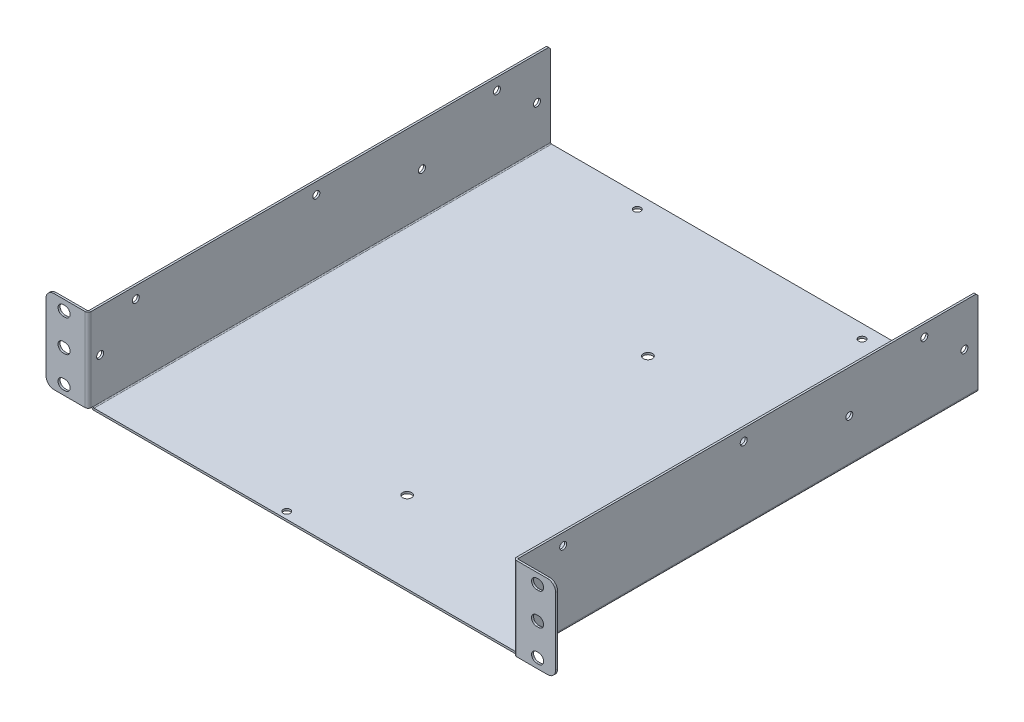
SolidWorks part; units mm, degrees
note: The reader was unsure of these and kept them because the rebuilt part matched: flange length of "Edge-Flange3", "Edge-Flange4", "Edge-Flange5", "Edge-Flange6".
ref_plane "Front Plane" through (0, 0, 0) normal (0, 0, 1) x (1, 0, 0)
ref_plane "Top Plane" through (0, 0, 0) normal (0, 1, 0) x (1, 0, 0)
ref_plane "Right Plane" through (0, 0, 0) normal (1, 0, 0) x (0, 0, -1)
sketch "Sketch1" plane through (0, 0, 0) normal (0, 1, 0) x (1, 0, 0)
  line L5 (-107, 115.25) -> (107, 115.25)
  line L6 (-107, 115.25) -> (-107, -115.25)
  line L7 (-107, -115.25) -> (107, -115.25)
  line L8 (107, 115.25) -> (107, -115.25)
  line L9 (-107, 115.25) -> (107, -115.25) construction
  line L10 (-107, -115.25) -> (107, 115.25) construction
  point P0 (0, 0)
  dimension "D1" = 214
  dimension "D2" = 230.5
base flange "Base-Flange1" sketch "Sketch1" thickness 1 reverse thickness direction no parameters "D1"=8
edge flange "Edge-Flange3" sketch "Sketch14" flange angle 90 flange length 43 flange position material inside bend radius 0.5 thickness 1 relief rectangular parameters "D6"=10
sketch "Sketch14" plane through (-107, 0, 0) normal (-1, 0, 0) x (0, 0, 1)
  line L0 (-115.25, 0) -> (115.25, 0) construction
  line L1 (-115.25, 0) -> (115.25, 0)
  line L2 (-115.25, 0) -> (-115.25, 42)
  line L3 (-115.25, 42) -> (115.25, 42)
  line L4 (115.25, 42) -> (115.25, 0)
bend "EdgeBend3" bend radius 0.5 bend angle 90 parameters "D5"=1
edge flange "Edge-Flange4" sketch "Sketch17" flange angle 90 flange length 43 flange position material inside bend radius 0.5 thickness 1 relief rectangular parameters "D6"=10
sketch "Sketch17" plane through (107, 0, 0) normal (1, 0, 0) x (0, 0, -1)
  line L0 (-115.25, 0) -> (115.25, 0) construction
  line L1 (-115.25, 0) -> (115.25, 0)
  line L2 (-115.25, 0) -> (-115.25, 42)
  line L3 (-115.25, 42) -> (115.25, 42)
  line L4 (115.25, 42) -> (115.25, 0)
bend "EdgeBend4" bend radius 0.5 bend angle 90 parameters "D5"=2
edge flange "Edge-Flange5" sketch "Sketch20" flange angle 90 flange length 21 flange position material inside bend radius 0.5 thickness 1 relief none parameters "D6"=10
sketch "Sketch20" plane through (107, 0, 115.25) normal (0, 0, 1) x (0, -1, 0)
  line L2 (-42, 0) -> (-42, 20)
  line L3 (-42, 20) -> (-0.5, 20)
  line L4 (-0.5, 20) -> (-0.5, 0)
  line L7 (-42, 0) -> (-0.5, 0) construction
  line L8 (-42, 0) -> (-0.5, 0)
bend "EdgeBend5" bend radius 0.5 bend angle 90 parameters "D5"=3
edge flange "Edge-Flange6" sketch "Sketch23" flange angle 90 flange length 21 flange position material inside bend radius 0.5 thickness 1 relief none parameters "D6"=10
sketch "Sketch23" plane through (-107, 0, 115.25) normal (0, 0, 1) x (0, 1, 0)
  line L0 (0.5, 0) -> (42, 0) construction
  line L1 (0.5, 0) -> (42, 0)
  line L2 (0.5, 0) -> (0.5, 20)
  line L3 (0.5, 20) -> (42, 20)
  line L4 (42, 20) -> (42, 0)
bend "EdgeBend6" bend radius 0.5 bend angle 90 parameters "D5"=4
fillet "Fillet1" radius 4 4 edges at (-127, 0.5, 114.75) (-127, 42, 114.75) (127, 0.5, 114.75) (127, 42, 114.75)
sketch "Sketch24" plane through (0, -1, 0) normal (0, -1, 0) x (1, 0, 0)
  line L0 (107, -115.25) -> (107, 113.75) construction
  line L1 (-107, 115.25) -> (107, 115.25)
  line L2 (-107, 115.25) -> (-107, 112.75)
  line L3 (-107, 112.75) -> (107, 112.75)
  line L4 (107, 115.25) -> (107, 112.75)
  dimension "D1" = 2.5
extrude "Cut-Extrude1" cut sketch "Sketch24" against normal up to surface (1.5 mm away) normal cut yes up to face at (115.25, 0.5, 114.75)
sketch "Sketch26" plane through (0, 0, 115.25) normal (0, 0, 1) x (1, 0, 0)
  line L0 (-118, 37) -> (-118, 5.24) construction
  line L1 (-118, 21.12) -> (-120.5, 21.12) construction
  line L3 (0, 0) -> (0, 21.12) construction
  line L4 (105.5, 0) -> (-105.5, 0) construction
  line L5 (0, 21.12) -> (-118, 21.12) construction
  line L6 (-118, 37) -> (-118, 42) construction
  line L7 (-107.5, 42) -> (-123, 42) construction
  circle A0 centre (-118, 37) radius 2.5
  circle A1 centre (-118, 5.24) radius 2.5
  circle A2 centre (-118, 21.12) radius 2.5
  circle A3 centre (118, 5.24) radius 2.5
  circle A4 centre (118, 21.12) radius 2.5
  circle A5 centre (118, 37) radius 2.5
  dimension "D1" = 31.76
  dimension "D2" = 5
  dimension "D3" = 118
  dimension "D4" = 5
extrude "Cut-Extrude2" cut sketch "Sketch26" against normal blind 10 normal cut yes
sketch "Sketch27" plane through (107, 0, 0) normal (1, 0, 0) x (0, 0, -1)
  circle A0 centre (-91.5, 36.25) radius 1.75
  circle A1 centre (-1.5, 36.25) radius 1.75
  circle A2 centre (88.5, 36.25) radius 1.75
  dimension "D1" = 3.5
extrude "Cut-Extrude3" cut sketch "Sketch27" against normal through all normal cut yes
sketch "Sketch28" plane through (0, -1, 0) normal (0, -1, 0) x (1, 0, 0)
  circle A0 centre (10, 72.25) radius 2.25
  circle A1 centre (85, 72.25) radius 2.25
  circle A2 centre (10, -47.75) radius 2.25
  circle A3 centre (85, -47.75) radius 2.25
  dimension "D1" = 4.5
extrude "Cut-Extrude4" cut sketch "Sketch28" against normal through all normal cut yes
sketch "Sketch29" plane through (0, 0, 0) normal (0, 1, 0) x (1, 0, 0)
  circle A0 centre (56, 108.45) radius 1.75
  circle A1 centre (-56, 108.45) radius 1.75
  dimension "D1" = 3.5
extrude "Cut-Extrude5" cut sketch "Sketch29" against normal through all normal cut yes
sketch "Sketch30" plane through (-107, 0, 0) normal (-1, 0, 0) x (0, 0, 1)
  line L0 (-115.25, 42) -> (-115.25, 0.5) construction
  line L1 (112.75, -1) -> (-115.25, -1) construction
  circle A0 centre (-51.1, 21) radius 1.75
  dimension "D1" = 64.15
  dimension "D3" = 3.5
  dimension "D2" = 22
extrude "Cut-Extrude6" cut sketch "Sketch30" against normal through all normal cut yes
sketch "Sketch31" plane through (-107, 0, 0) normal (-1, 0, 0) x (0, 0, 1)
  circle A0 centre (-108.45, 21) radius 1.75
  dimension "D1" = 3.5
extrude "Cut-Extrude7" cut sketch "Sketch31" against normal through all normal cut yes
chamfer "Chamfer1" distance 1 angle 45 2 edges at (106.5, 42, -115.25) (-106.5, 42, -115.25)
sketch "Sketch32" plane through (0, 0, 114.25) normal (0, 0, -1) x (-1, 0, 0)
  line L0 (117.5, 37) -> (118.5, 37) construction
  line L1 (117.5, 39.5) -> (118.5, 39.5)
  line L2 (117.5, 34.5) -> (118.5, 34.5)
  line L3 (117.5, 21.12) -> (118.5, 21.12) construction
  line L4 (117.5, 23.62) -> (118.5, 23.62)
  line L5 (117.5, 18.62) -> (118.5, 18.62)
  line L6 (117.5, 5.24) -> (118.5, 5.24) construction
  line L7 (117.5, 7.74) -> (118.5, 7.74)
  line L8 (117.5, 2.74) -> (118.5, 2.74)
  line L9 (0, -1) -> (0, -11.9276) construction
  line L10 (-105.5, -1) -> (105.5, -1) construction
  arc A0 (117.5, 39.5) -> (117.5, 34.5) centre (117.5, 37) ccw
  arc A1 (118.5, 34.5) -> (118.5, 39.5) centre (118.5, 37) ccw
  arc A3 (117.5, 23.62) -> (117.5, 18.62) centre (117.5, 21.12) ccw
  arc A4 (118.5, 18.62) -> (118.5, 23.62) centre (118.5, 21.12) ccw
  arc A5 (117.5, 7.74) -> (117.5, 2.74) centre (117.5, 5.24) ccw
  arc A6 (118.5, 2.74) -> (118.5, 7.74) centre (118.5, 5.24) ccw
  point P2 (118, 37)
  point P15 (118, 21.12)
  point P22 (118, 5.24)
  dimension "D2" = 2.5
  dimension "D3" = 3
  dimension "D1" = 1
  dimension "D4" = 15.88
extrude "Cut-Extrude8" cut sketch "Sketch32" against normal through all normal cut yes
mirror "Mirror1" about plane through (0, 0, 0) normal (1, 0, 0) of "Cut-Extrude8"
sketch "Sketch33" plane through (0, -1, 0) normal (0, -1, 0) x (1, 0, 0)
  circle A0 centre (-13, 109.25) radius 1.75
  dimension "D1" = 3.5
extrude "Cut-Extrude9" cut sketch "Sketch33" against normal through all normal cut yes
sketch "Sketch34" plane through (-107, 0, 0) normal (-1, 0, 0) x (0, 0, 1)
  circle A0 centre (109.25, 21) radius 1.75
  dimension "D1" = 3.5
extrude "Cut-Extrude10" cut sketch "Sketch34" against normal through all normal cut yes
sketch "Bend-Lines1" [suppressed] plane through (0, 0, 0) normal (0, 1, 0) x (1, 0, 0)
sketch "Bounding-Box1" [suppressed] plane through (0, 0, 0) normal (0, 1, 0) x (1, 0, 0)
sheet metal parameters "Sheet-Metal1" thickness 1 parameters "D1"=8
flat pattern "Flat-Pattern1" [suppressed]
sketch "Bend-Lines2" plane through (0, 0, 0) normal (0, 1, 0) x (1, 0, 0)
sketch3d "Bounding-Box2" [suppressed]
  line L0 (-107, 115.25, 0) -> (-107, -115.25, 0) construction
  line L1 (107, 115.25, 0) -> (107, -115.25, 0) construction
  line L2 (-107, 115.25, 0) -> (107, 115.25, 0) construction
  line L3 (-107, -115.25, 0) -> (107, -115.25, 0) construction
sheet metal parameters "Sheet-Metal4" thickness 1 parameters "D1"=8
flat pattern "Flat-Pattern1"
sketch "Bend-Lines2" plane through (0, 0, 0) normal (0, 1, 0) x (1, 0, 0)
  line L0 (-107.2854, 115.25) -> (-107.2854, -115.25) construction
  line L1 (-107.2854, 115.25) -> (-107.2854, -115.25) construction
sketch3d "Bounding-Box2" [suppressed]
  line L0 (107, -115.25, 0) -> (-150.5708, -115.25, 0) construction
  line L1 (107, 115.25, 0) -> (-150.5708, 115.25, 0) construction
  line L2 (107, -115.25, 0) -> (107, 115.25, 0) construction
  line L3 (-150.5708, -115.25, 0) -> (-150.5708, 115.25, 0) construction
bend of the flat pattern "Flatten-<EdgeBend3>1"
sheet metal parameters "Sheet-Metal5" thickness 1 parameters "D1"=8
flat pattern "Flat-Pattern1"
sketch "Bend-Lines2" plane through (0, 0, 0) normal (0, 1, 0) x (1, 0, 0)
  line L0 (-107.2854, 115.25) -> (-107.2854, -115.25) construction
  line L1 (-107.2854, 115.25) -> (-107.2854, -115.25) construction
  line L2 (107.2854, -115.25) -> (107.2854, 115.25) construction
  line L3 (107.2854, -115.25) -> (107.2854, 115.25) construction
sketch3d "Bounding-Box2" [suppressed]
  line L0 (150.5708, -115.25, 0) -> (-150.5708, -115.25, 0) construction
  line L1 (150.5708, 115.25, 0) -> (-150.5708, 115.25, 0) construction
  line L2 (150.5708, -115.25, 0) -> (150.5708, 115.25, 0) construction
  line L3 (-150.5708, -115.25, 0) -> (-150.5708, 115.25, 0) construction
bend of the flat pattern "Flatten-<EdgeBend3>1"
bend of the flat pattern "Flatten-<EdgeBend4>1"
sheet metal parameters "Sheet-Metal6" thickness 1 parameters "D1"=8
flat pattern "Flat-Pattern1"
sketch "Bend-Lines2" plane through (0, 0, 0) normal (0, 1, 0) x (1, 0, 0)
  line L0 (-107.2854, 115.25) -> (-107.2854, -115.25) construction
  line L1 (-107.2854, 115.25) -> (-107.2854, -115.25) construction
  line L2 (107.2854, -115.25) -> (107.2854, 115.25) construction
  line L3 (107.2854, -115.25) -> (107.2854, 115.25) construction
  line L4 (108.0708, -114.5354) -> (150.5708, -114.5354) construction
  line L5 (108.0708, -114.5354) -> (150.5708, -114.5354) construction
sketch3d "Bounding-Box2" [suppressed]
  line L0 (150.5708, -133.8208, 0) -> (-150.5708, -133.8208, 0) construction
  line L1 (150.5708, 115.25, 0) -> (-150.5708, 115.25, 0) construction
  line L2 (150.5708, -133.8208, 0) -> (150.5708, 115.25, 0) construction
  line L3 (-150.5708, -133.8208, 0) -> (-150.5708, 115.25, 0) construction
bend of the flat pattern "Flatten-<EdgeBend3>1"
bend of the flat pattern "Flatten-<EdgeBend4>1"
bend of the flat pattern "Flatten-<EdgeBend5>1"
sheet metal parameters "Sheet-Metal7" thickness 1 parameters "D1"=8
flat pattern "Flat-Pattern1"
sketch "Bend-Lines2" plane through (0, 0, 0) normal (0, 1, 0) x (1, 0, 0)
  line L0 (-107.2854, -115.25) -> (-107.2854, 115.25) construction
  line L1 (-107.2854, -115.25) -> (-107.2854, 115.25) construction
  line L2 (107.2854, -115.25) -> (107.2854, 115.25) construction
  line L3 (107.2854, -115.25) -> (107.2854, 115.25) construction
  line L4 (108.0708, -114.5354) -> (150.5708, -114.5354) construction
  line L5 (108.0708, -114.5354) -> (150.5708, -114.5354) construction
  line L6 (-150.5708, -114.5354) -> (-108.0708, -114.5354) construction
  line L7 (-150.5708, -114.5354) -> (-108.0708, -114.5354) construction
sketch3d "Bounding-Box2" [suppressed]
  line L0 (-150.5708, -133.8208, 0) -> (150.5708, -133.8208, 0) construction
  line L1 (-150.5708, 115.25, 0) -> (150.5708, 115.25, 0) construction
  line L2 (-150.5708, -133.8208, 0) -> (-150.5708, 115.25, 0) construction
  line L3 (150.5708, -133.8208, 0) -> (150.5708, 115.25, 0) construction
bend of the flat pattern "Flatten-<EdgeBend3>1"
bend of the flat pattern "Flatten-<EdgeBend4>1"
bend of the flat pattern "Flatten-<EdgeBend5>1"
bend of the flat pattern "Flatten-<EdgeBend6>1"
sheet metal parameters "Sheet-Metal8" thickness 1 parameters "D1"=8
flat pattern "Flat-Pattern1"
sketch "Bend-Lines2" plane through (0, 0, 0) normal (0, 1, 0) x (1, 0, 0)
  line L0 (-107.2854, 115.25) -> (-107.2854, -112.75) construction
  line L1 (-107.2854, 115.25) -> (-107.2854, -112.75) construction
  line L2 (107.2854, -112.75) -> (107.2854, 115.25) construction
  line L3 (107.2854, -112.75) -> (107.2854, 115.25) construction
  line L4 (108.0708, -114.5354) -> (150.5708, -114.5354) construction
  line L5 (108.0708, -114.5354) -> (150.5708, -114.5354) construction
  line L6 (-150.5708, -114.5354) -> (-108.0708, -114.5354) construction
  line L7 (-150.5708, -114.5354) -> (-108.0708, -114.5354) construction
sketch3d "Bounding-Box2" [suppressed]
  line L0 (-150.5708, -133.8208, 0) -> (150.5708, -133.8208, 0) construction
  line L1 (-150.5708, 115.25, 0) -> (150.5708, 115.25, 0) construction
  line L2 (-150.5708, -133.8208, 0) -> (-150.5708, 115.25, 0) construction
  line L3 (150.5708, -133.8208, 0) -> (150.5708, 115.25, 0) construction
bend of the flat pattern "Flatten-<EdgeBend3>1"
bend of the flat pattern "Flatten-<EdgeBend4>1"
bend of the flat pattern "Flatten-<EdgeBend5>1"
bend of the flat pattern "Flatten-<EdgeBend6>1"
sheet metal parameters "Sheet-Metal9" thickness 1 parameters "D1"=8
flat pattern "Flat-Pattern1"
sketch "Bend-Lines2" plane through (0, 0, 0) normal (0, 1, 0) x (1, 0, 0)
  line L0 (-106.2854, 115.25) -> (-106.2854, -112.75) construction
  line L1 (-106.2854, 115.25) -> (-106.2854, -112.75) construction
  line L2 (106.2854, -112.75) -> (106.2854, 115.25) construction
  line L3 (106.2854, -112.75) -> (106.2854, 115.25) construction
  line L4 (107.0708, -114.5354) -> (148.5708, -114.5354) construction
  line L5 (107.0708, -114.5354) -> (148.5708, -114.5354) construction
  line L6 (-148.5708, -114.5354) -> (-107.0708, -114.5354) construction
  line L7 (-148.5708, -114.5354) -> (-107.0708, -114.5354) construction
sketch3d "Bounding-Box2" [suppressed]
  line L0 (-148.5708, -134.8206, 0) -> (148.5708, -134.8208, 0) construction
  line L1 (-148.5707, 115.25, 0) -> (148.5709, 115.2498, 0) construction
  line L2 (-148.5708, -134.8206, 0) -> (-148.5707, 115.25, 0) construction
  line L3 (148.5708, -134.8208, 0) -> (148.5709, 115.2498, 0) construction
bend of the flat pattern "Flatten-<EdgeBend3>1"
bend of the flat pattern "Flatten-<EdgeBend4>1"
bend of the flat pattern "Flatten-<EdgeBend5>1"
bend of the flat pattern "Flatten-<EdgeBend6>1"
sheet metal parameters "Sheet-Metal10" thickness 1 parameters "D1"=8
flat pattern "Flat-Pattern1"
sketch "Bend-Lines2" plane through (0, 0, 0) normal (0, 1, 0) x (1, 0, 0)
  line L0 (-106.2854, 115.25) -> (-106.2854, -112.75) construction
  line L1 (-106.2854, 115.25) -> (-106.2854, -112.75) construction
  line L2 (106.2854, -112.75) -> (106.2854, 115.25) construction
  line L3 (106.2854, -112.75) -> (106.2854, 115.25) construction
  line L4 (107.0708, -114.5354) -> (148.5708, -114.5354) construction
  line L5 (107.0708, -114.5354) -> (148.5708, -114.5354) construction
  line L6 (-148.5708, -114.5354) -> (-107.0708, -114.5354) construction
  line L7 (-148.5708, -114.5354) -> (-107.0708, -114.5354) construction
sketch3d "Bounding-Box2" [suppressed]
  line L0 (-148.5708, -134.8206, 0) -> (148.5708, -134.8208, 0) construction
  line L1 (-148.5707, 115.25, 0) -> (148.5709, 115.2498, 0) construction
  line L2 (-148.5708, -134.8206, 0) -> (-148.5707, 115.25, 0) construction
  line L3 (148.5708, -134.8208, 0) -> (148.5709, 115.2498, 0) construction
bend of the flat pattern "Flatten-<EdgeBend3>1"
bend of the flat pattern "Flatten-<EdgeBend4>1"
bend of the flat pattern "Flatten-<EdgeBend5>1"
bend of the flat pattern "Flatten-<EdgeBend6>1"
sheet metal parameters "Sheet-Metal11" thickness 1 parameters "D1"=8
flat pattern "Flat-Pattern1"
sketch "Bend-Lines2" plane through (0, 0, 0) normal (0, 1, 0) x (1, 0, 0)
  line L0 (-106.2854, 115.25) -> (-106.2854, -112.75) construction
  line L1 (-106.2854, 115.25) -> (-106.2854, -112.75) construction
  line L2 (106.2854, -112.75) -> (106.2854, 115.25) construction
  line L3 (106.2854, -112.75) -> (106.2854, 115.25) construction
  line L4 (107.0708, -114.5354) -> (148.5708, -114.5354) construction
  line L5 (107.0708, -114.5354) -> (148.5708, -114.5354) construction
  line L6 (-148.5708, -114.5354) -> (-107.0708, -114.5354) construction
  line L7 (-148.5708, -114.5354) -> (-107.0708, -114.5354) construction
sketch3d "Bounding-Box2" [suppressed]
  line L0 (-148.5708, -134.8206, 0) -> (148.5708, -134.8208, 0) construction
  line L1 (-148.5707, 115.25, 0) -> (148.5709, 115.2498, 0) construction
  line L2 (-148.5708, -134.8206, 0) -> (-148.5707, 115.25, 0) construction
  line L3 (148.5708, -134.8208, 0) -> (148.5709, 115.2498, 0) construction
bend of the flat pattern "Flatten-<EdgeBend3>1"
bend of the flat pattern "Flatten-<EdgeBend4>1"
bend of the flat pattern "Flatten-<EdgeBend5>1"
bend of the flat pattern "Flatten-<EdgeBend6>1"
sheet metal parameters "Sheet-Metal12" thickness 1 parameters "D1"=8
flat pattern "Flat-Pattern1"
sketch "Bend-Lines2" plane through (0, 0, 0) normal (0, 1, 0) x (1, 0, 0)
  line L0 (-106.2854, 115.25) -> (-106.2854, -112.75) construction
  line L1 (-106.2854, 115.25) -> (-106.2854, -112.75) construction
  line L2 (106.2854, -112.75) -> (106.2854, 115.25) construction
  line L3 (106.2854, -112.75) -> (106.2854, 115.25) construction
  line L4 (107.0708, -114.5354) -> (148.5708, -114.5354) construction
  line L5 (107.0708, -114.5354) -> (148.5708, -114.5354) construction
  line L6 (-148.5708, -114.5354) -> (-107.0708, -114.5354) construction
  line L7 (-148.5708, -114.5354) -> (-107.0708, -114.5354) construction
sketch3d "Bounding-Box2" [suppressed]
  line L0 (-148.5708, -134.8206, 0) -> (148.5708, -134.8208, 0) construction
  line L1 (-148.5707, 115.25, 0) -> (148.5709, 115.2498, 0) construction
  line L2 (-148.5708, -134.8206, 0) -> (-148.5707, 115.25, 0) construction
  line L3 (148.5708, -134.8208, 0) -> (148.5709, 115.2498, 0) construction
bend of the flat pattern "Flatten-<EdgeBend3>1"
bend of the flat pattern "Flatten-<EdgeBend4>1"
bend of the flat pattern "Flatten-<EdgeBend5>1"
bend of the flat pattern "Flatten-<EdgeBend6>1"
sheet metal parameters "Sheet-Metal13" thickness 1 parameters "D1"=8
flat pattern "Flat-Pattern1"
sketch "Bend-Lines2" plane through (0, 0, 0) normal (0, 1, 0) x (1, 0, 0)
  line L0 (-106.2854, 115.25) -> (-106.2854, -112.75) construction
  line L1 (-106.2854, 115.25) -> (-106.2854, -112.75) construction
  line L2 (106.2854, -112.75) -> (106.2854, 115.25) construction
  line L3 (106.2854, -112.75) -> (106.2854, 115.25) construction
  line L4 (107.0708, -114.5354) -> (148.5708, -114.5354) construction
  line L5 (107.0708, -114.5354) -> (148.5708, -114.5354) construction
  line L6 (-148.5708, -114.5354) -> (-107.0708, -114.5354) construction
  line L7 (-148.5708, -114.5354) -> (-107.0708, -114.5354) construction
sketch3d "Bounding-Box2" [suppressed]
  line L0 (-148.5708, -134.8206, 0) -> (148.5708, -134.8208, 0) construction
  line L1 (-148.5707, 115.25, 0) -> (148.5709, 115.2498, 0) construction
  line L2 (-148.5708, -134.8206, 0) -> (-148.5707, 115.25, 0) construction
  line L3 (148.5708, -134.8208, 0) -> (148.5709, 115.2498, 0) construction
bend of the flat pattern "Flatten-<EdgeBend3>1"
bend of the flat pattern "Flatten-<EdgeBend4>1"
bend of the flat pattern "Flatten-<EdgeBend5>1"
bend of the flat pattern "Flatten-<EdgeBend6>1"
sheet metal parameters "Sheet-Metal14" thickness 1 parameters "D1"=8
flat pattern "Flat-Pattern1"
sketch "Bend-Lines2" plane through (0, 0, 0) normal (0, 1, 0) x (1, 0, 0)
  line L0 (-106.2854, 115.25) -> (-106.2854, -112.75) construction
  line L1 (-106.2854, 115.25) -> (-106.2854, -112.75) construction
  line L2 (106.2854, -112.75) -> (106.2854, 115.25) construction
  line L3 (106.2854, -112.75) -> (106.2854, 115.25) construction
  line L4 (107.0708, -114.5354) -> (148.5708, -114.5354) construction
  line L5 (107.0708, -114.5354) -> (148.5708, -114.5354) construction
  line L6 (-148.5708, -114.5354) -> (-107.0708, -114.5354) construction
  line L7 (-148.5708, -114.5354) -> (-107.0708, -114.5354) construction
sketch3d "Bounding-Box2" [suppressed]
  line L0 (-148.5708, -134.8206, 0) -> (148.5708, -134.8208, 0) construction
  line L1 (-148.5707, 115.25, 0) -> (148.5709, 115.2498, 0) construction
  line L2 (-148.5708, -134.8206, 0) -> (-148.5707, 115.25, 0) construction
  line L3 (148.5708, -134.8208, 0) -> (148.5709, 115.2498, 0) construction
bend of the flat pattern "Flatten-<EdgeBend3>1"
bend of the flat pattern "Flatten-<EdgeBend4>1"
bend of the flat pattern "Flatten-<EdgeBend5>1"
bend of the flat pattern "Flatten-<EdgeBend6>1"
sheet metal parameters "Sheet-Metal15" thickness 1 parameters "D1"=8
flat pattern "Flat-Pattern1"
sketch "Bend-Lines2" plane through (0, 0, 0) normal (0, 1, 0) x (1, 0, 0)
  line L0 (-106.2854, 115.25) -> (-106.2854, -112.75) construction
  line L1 (-106.2854, 115.25) -> (-106.2854, -112.75) construction
  line L2 (106.2854, -112.75) -> (106.2854, 115.25) construction
  line L3 (106.2854, -112.75) -> (106.2854, 115.25) construction
  line L4 (107.0708, -114.5354) -> (148.5708, -114.5354) construction
  line L5 (107.0708, -114.5354) -> (148.5708, -114.5354) construction
  line L6 (-148.5708, -114.5354) -> (-107.0708, -114.5354) construction
  line L7 (-148.5708, -114.5354) -> (-107.0708, -114.5354) construction
sketch3d "Bounding-Box2" [suppressed]
  line L0 (-148.5708, -134.8206, 0) -> (148.5708, -134.8208, 0) construction
  line L1 (-148.5707, 115.25, 0) -> (148.5709, 115.2498, 0) construction
  line L2 (-148.5708, -134.8206, 0) -> (-148.5707, 115.25, 0) construction
  line L3 (148.5708, -134.8208, 0) -> (148.5709, 115.2498, 0) construction
bend of the flat pattern "Flatten-<EdgeBend3>1"
bend of the flat pattern "Flatten-<EdgeBend4>1"
bend of the flat pattern "Flatten-<EdgeBend5>1"
bend of the flat pattern "Flatten-<EdgeBend6>1"
sheet metal parameters "Sheet-Metal16" thickness 1 parameters "D1"=8
flat pattern "Flat-Pattern1"
sketch "Bend-Lines2" plane through (0, 0, 0) normal (0, 1, 0) x (1, 0, 0)
  line L0 (-106.2854, 115.25) -> (-106.2854, -112.75) construction
  line L1 (-106.2854, 115.25) -> (-106.2854, -112.75) construction
  line L2 (106.2854, -112.75) -> (106.2854, 115.25) construction
  line L3 (106.2854, -112.75) -> (106.2854, 115.25) construction
  line L4 (107.0708, -114.5354) -> (148.5708, -114.5354) construction
  line L5 (107.0708, -114.5354) -> (148.5708, -114.5354) construction
  line L6 (-148.5708, -114.5354) -> (-107.0708, -114.5354) construction
  line L7 (-148.5708, -114.5354) -> (-107.0708, -114.5354) construction
sketch3d "Bounding-Box2" [suppressed]
  line L0 (-148.5708, -134.8206, 0) -> (148.5708, -134.8208, 0) construction
  line L1 (-148.5707, 115.25, 0) -> (148.5709, 115.2498, 0) construction
  line L2 (-148.5708, -134.8206, 0) -> (-148.5707, 115.25, 0) construction
  line L3 (148.5708, -134.8208, 0) -> (148.5709, 115.2498, 0) construction
bend of the flat pattern "Flatten-<EdgeBend3>1"
bend of the flat pattern "Flatten-<EdgeBend4>1"
bend of the flat pattern "Flatten-<EdgeBend5>1"
bend of the flat pattern "Flatten-<EdgeBend6>1"
sheet metal parameters "Sheet-Metal17" thickness 1 parameters "D1"=8
flat pattern "Flat-Pattern1"
sketch "Bend-Lines2" plane through (0, 0, 0) normal (0, 1, 0) x (1, 0, 0)
  line L0 (-106.2854, 115.25) -> (-106.2854, -112.75) construction
  line L1 (-106.2854, 115.25) -> (-106.2854, -112.75) construction
  line L2 (106.2854, -112.75) -> (106.2854, 115.25) construction
  line L3 (106.2854, -112.75) -> (106.2854, 115.25) construction
  line L4 (107.0708, -114.5354) -> (148.5708, -114.5354) construction
  line L5 (107.0708, -114.5354) -> (148.5708, -114.5354) construction
  line L6 (-148.5708, -114.5354) -> (-107.0708, -114.5354) construction
  line L7 (-148.5708, -114.5354) -> (-107.0708, -114.5354) construction
sketch3d "Bounding-Box2" [suppressed]
  line L0 (-148.5708, -134.8206, 0) -> (148.5708, -134.8208, 0) construction
  line L1 (-148.5707, 115.25, 0) -> (148.5709, 115.2498, 0) construction
  line L2 (-148.5708, -134.8206, 0) -> (-148.5707, 115.25, 0) construction
  line L3 (148.5708, -134.8208, 0) -> (148.5709, 115.2498, 0) construction
bend of the flat pattern "Flatten-<EdgeBend3>1"
bend of the flat pattern "Flatten-<EdgeBend4>1"
bend of the flat pattern "Flatten-<EdgeBend5>1"
bend of the flat pattern "Flatten-<EdgeBend6>1"
sheet metal parameters "Sheet-Metal18" thickness 1 parameters "D1"=8
flat pattern "Flat-Pattern1"
sketch "Bend-Lines2" plane through (0, 0, 0) normal (0, 1, 0) x (1, 0, 0)
  line L0 (-106.2854, 115.25) -> (-106.2854, -112.75) construction
  line L1 (-106.2854, 115.25) -> (-106.2854, -112.75) construction
  line L2 (106.2854, -112.75) -> (106.2854, 115.25) construction
  line L3 (106.2854, -112.75) -> (106.2854, 115.25) construction
  line L4 (107.0708, -114.5354) -> (148.5708, -114.5354) construction
  line L5 (107.0708, -114.5354) -> (148.5708, -114.5354) construction
  line L6 (-148.5708, -114.5354) -> (-107.0708, -114.5354) construction
  line L7 (-148.5708, -114.5354) -> (-107.0708, -114.5354) construction
sketch3d "Bounding-Box2" [suppressed]
  line L0 (-148.5708, -134.8206, 0) -> (148.5708, -134.8208, 0) construction
  line L1 (-148.5707, 115.25, 0) -> (148.5709, 115.2498, 0) construction
  line L2 (-148.5708, -134.8206, 0) -> (-148.5707, 115.25, 0) construction
  line L3 (148.5708, -134.8208, 0) -> (148.5709, 115.2498, 0) construction
bend of the flat pattern "Flatten-<EdgeBend3>1"
bend of the flat pattern "Flatten-<EdgeBend4>1"
bend of the flat pattern "Flatten-<EdgeBend5>1"
bend of the flat pattern "Flatten-<EdgeBend6>1"
